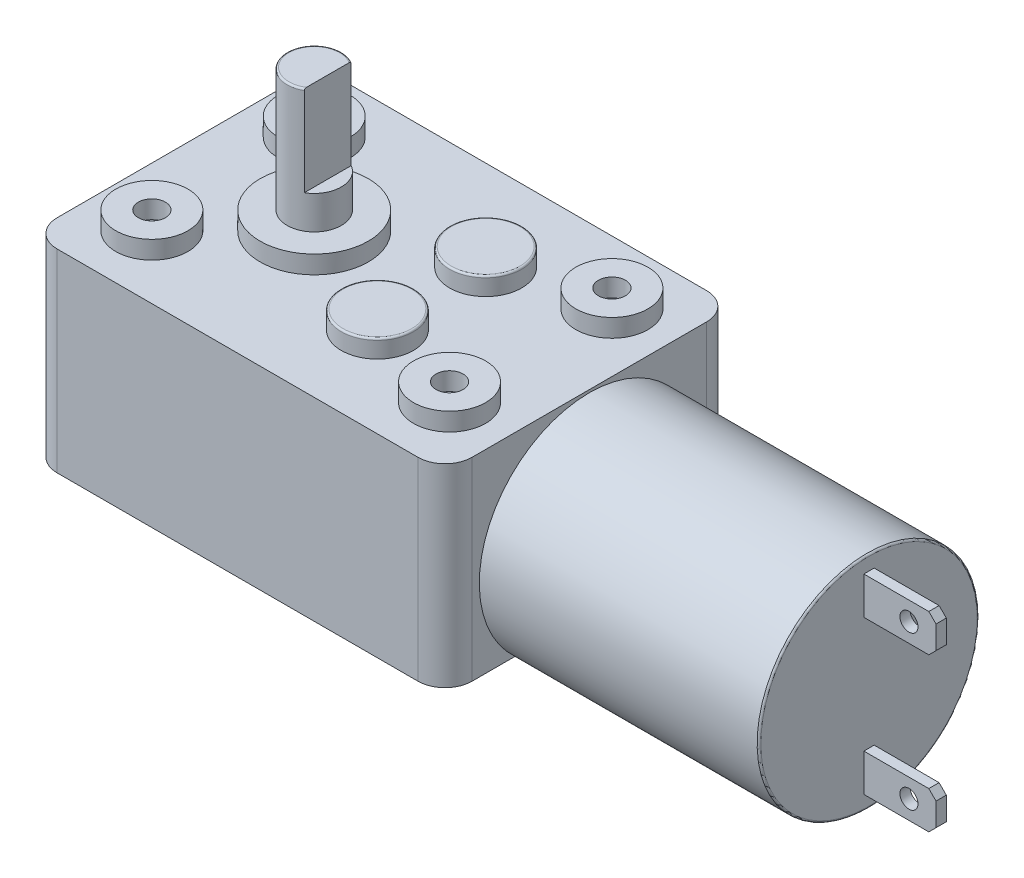
SolidWorks part; units mm, degrees
ref_plane "Front Plane" through (0, 0, 0) normal (0, 0, 1) x (1, 0, 0)
ref_plane "Top Plane" through (0, 0, 0) normal (0, 1, 0) x (1, 0, 0)
ref_plane "Right Plane" through (0, 0, 0) normal (1, 0, 0) x (0, 0, -1)
sketch "Sketch1" plane through (0, 0, 0) normal (0, 1, 0) x (1, 0, 0)
  line L1 (0, 0) -> (46, 0)
  line L2 (0, 0) -> (0, 32)
  line L3 (0, 32) -> (46, 32)
  line L4 (46, 0) -> (46, 32)
  dimension "D1" = 32
  dimension "D2" = 46
extrude "Boss-Extrude1" add sketch "Sketch1" along normal blind 21.5
sketch "Sketch2" plane through (0, 21.5, 0) normal (0, 1, 0) x (1, 0, 0)
  line L0 (0, 16) -> (46, 16) construction
  line L1 (0, 32) -> (0, 0) construction
  line L2 (46, 0) -> (46, 32) construction
  line L3 (0, 16) -> (6.5, 16) construction
  line L4 (6.5, 16) -> (6.5, 25) construction
  line L5 (6.5, 25) -> (39.5, 25) construction
  line L6 (39.5, 16) -> (39.5, 25) construction
  line L7 (6.5, 7) -> (39.5, 7) construction
  circle A0 centre (6.5, 25) radius 4
  circle A1 centre (6.5, 25) radius 1.5
  circle A2 centre (39.5, 25) radius 1.5
  circle A3 centre (39.5, 25) radius 4
  circle A4 centre (39.5, 7) radius 4
  circle A5 centre (39.5, 7) radius 1.5
  circle A6 centre (6.5, 7) radius 1.5
  circle A7 centre (6.5, 7) radius 4
  dimension "D4" = 8
  dimension "D5" = 3
  dimension "D6" = 8
  dimension "D7" = 3
  dimension "D1" = 6.5
  dimension "D2" = 9
  dimension "D3" = 33
extrude "Boss-Extrude2" add sketch "Sketch2" along normal blind 2
fillet "Fillet1" radius 3 1 edges at (46, 10.75, -32)
fillet "Fillet2" radius 3 3 edges at (46, 10.75, 0) (0, 10.75, 0) (0, 10.75, -32)
sketch "Sketch3" plane through (0, 21.5, 0) normal (0, 1, 0) x (1, 0, 0)
  line L0 (0, 16) -> (15.5, 16) construction
  line L1 (0, 29) -> (0, 3) construction
  circle A0 centre (15.5, 16) radius 3
  dimension "D2" = 6
  dimension "D1" = 15.5
extrude "Boss-Extrude3" add sketch "Sketch3" along normal blind 15.7
sketch "Sketch5" plane through (0, 37.2, 0) normal (0, 1, 0) x (1, 0, 0)
  line L0 (17, 18.5981) -> (17, 13.4019)
  line L1 (17, 16) -> (17, 18.5981) construction
  line L2 (17, 18.5981) -> (17, 13.4019) construction
  circle A0 centre (15.5, 16) radius 3 construction
  circle A1 centre (15.5, 16) radius 3 construction
  arc A2 (17, 13.4019) -> (17, 18.5981) centre (15.5, 16) ccw
extrude "Cut-Extrude1" cut sketch "Sketch5" against normal blind 10
sketch "Sketch6" plane through (0, 21.5, 0) normal (0, 1, 0) x (1, 0, 0)
  circle A0 centre (15.5, 16) radius 6
  dimension "D1" = 12
extrude "Boss-Extrude4" add sketch "Sketch6" along normal blind 2
sketch "Sketch7" plane through (46, 0, 0) normal (1, 0, 0) x (0, 0, -1)
  line L0 (16, 21.5) -> (16, 9) construction
  line L1 (3, 21.5) -> (29, 21.5) construction
  circle A0 centre (16, 9) radius 12.2
  dimension "D2" = 24.4
  dimension "D1" = 12.5
extrude "Boss-Extrude5" add sketch "Sketch7" along normal blind 31
sketch "Sketch8" plane through (77, 0, 0) normal (1, 0, 0) x (0, 0, -1)
  line L0 (16, 21.2) -> (16, -3.2) construction
  line L1 (16, 0.5) -> (16, 17.5) construction
  line L2 (16, 9) -> (28.2, 9) construction
  line L3 (15.4297, 19.5797) -> (16.5703, 19.5797)
  line L4 (15.4297, 19.5797) -> (15.4297, 15.4203)
  line L5 (15.4297, 15.4203) -> (16.5703, 15.4203)
  line L6 (16.5703, 19.5797) -> (16.5703, 15.4203)
  line L7 (16.5703, -1.5797) -> (16.5703, 2.5797)
  line L8 (15.4297, 2.5797) -> (16.5703, 2.5797)
  line L9 (15.4297, -1.5797) -> (15.4297, 2.5797)
  line L10 (15.4297, -1.5797) -> (16.5703, -1.5797)
  circle A0 centre (16, 9) radius 12.2 construction
  arc A1 (24.2365, 0) -> (7.7635, 0) centre (16, 9) ccw construction
  dimension "D1" = 8.5
  dimension "D2" = 4.1594
  dimension "D3" = 1.1406
extrude "Boss-Extrude6" add sketch "Sketch8" along normal blind 8
chamfer "Chamfer1" distance 0.8 angle 45 1 edges at (85, 19.5797, -16)
chamfer "Chamfer2" distance 0.8 angle 45 3 edges at (85, -1.5797, -16) (85, 2.5797, -16) (85, 15.4203, -16)
sketch "Sketch9" plane through (0, 0, -15.4297) normal (0, 0, 1) x (1, 0, 0)
  line L0 (85, 17.5) -> (82, 17.5) construction
  line L1 (85, 18.7797) -> (85, 16.2203) construction
  line L3 (85, 1.7797) -> (85, -0.7797) construction
  line L4 (85, 0.5) -> (82, 0.5) construction
  circle A0 centre (82, 17.5) radius 1
  circle A1 centre (82, 0.5) radius 1
  dimension "D2" = 2
  dimension "D3" = 2
  dimension "D1" = 3
extrude "Cut-Extrude2" cut sketch "Sketch9" against normal blind 8
sketch "Sketch10" plane through (0, 21.5, 0) normal (0, 1, 0) x (1, 0, 0)
  line L0 (46, 16) -> (21.5, 16) construction
  line L1 (46, 3) -> (46, 29) construction
  line L2 (46, 16) -> (28.5, 16) construction
  line L3 (28.5, 16) -> (28.5, 22) construction
  circle A0 centre (15.5, 16) radius 6 construction
  circle A1 centre (28.5, 22) radius 4
  circle A2 centre (28.5, 10) radius 4
  dimension "D3" = 8
  dimension "D1" = 17.5
  dimension "D2" = 6
extrude "Boss-Extrude7" add sketch "Sketch10" along normal blind 2
fillet "Fillet3" radius 0.2 1 edges at (28.5, 23.5, -14)
fillet "Fillet4" radius 0.2 1 edges at (28.5, 23.5, -18)
fillet "Fillet5" radius 0.2 1 edges at (12.5, 37.2, -16)
fillet "Fillet6" radius 0.2 1 edges at (77, 9, -28.2)
fillet "Fillet7" radius 0.3 1 edges at (46, -3.2, -16)
scale "Scale3" scale about centroid uniform scaling yes scale factor 0.6
